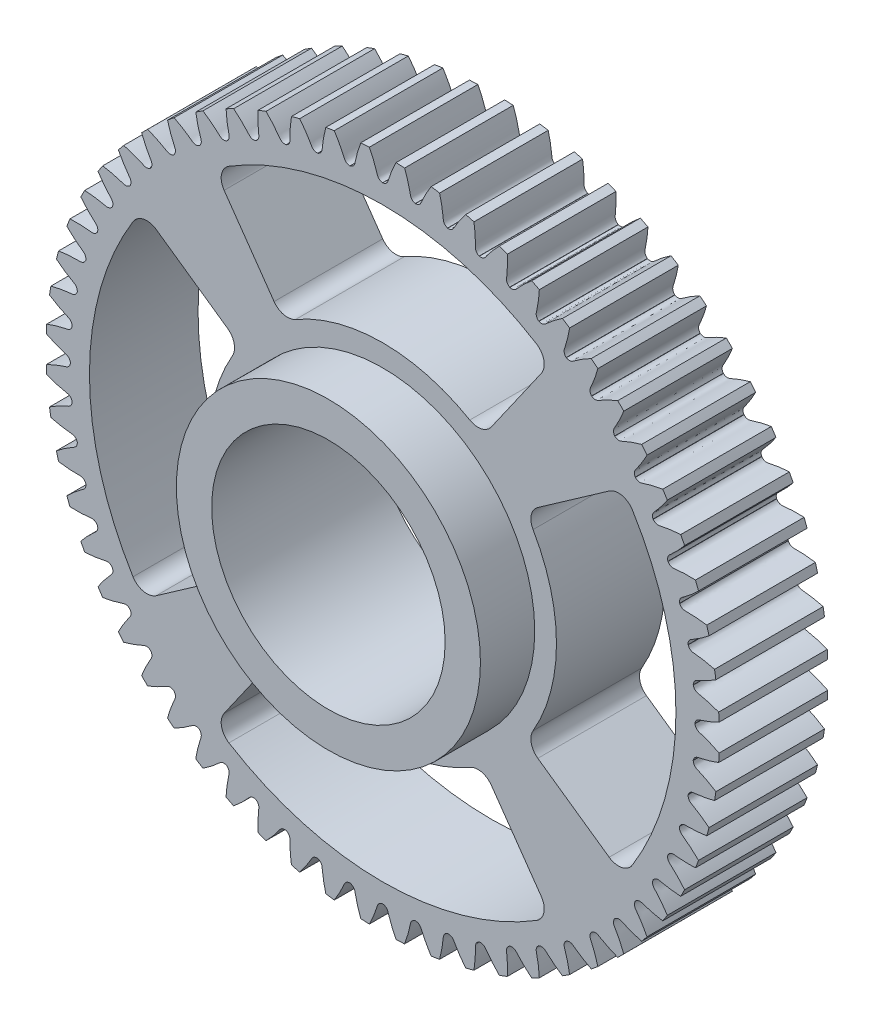
SolidWorks part; units mm, degrees
ref_plane "前视基准面" through (0, 0, 0) normal (0, 0, 1) x (1, 0, 0)
ref_plane "上视基准面" through (0, 0, 0) normal (0, 1, 0) x (1, 0, 0)
ref_plane "右视基准面" through (0, 0, 0) normal (1, 0, 0) x (0, 0, -1)
other "Configuration Table"
sketch "草图1" plane through (0, 0, 0) normal (0, 0, 1) x (1, 0, 0)
  circle A0 centre (0, 0) radius 31
extrude "凸台-拉伸1" add sketch "草图1" along normal blind 10
ref_axis "基准轴1" through (0, 0, -1.5) along (0, 0, 1)
sketch "草图2" plane through (0, 0, 0) normal (0, 0, 1) x (1, 0, 0)
  line L0 (0, 0) -> (0, 31) construction
  circle A0 centre (0, 0) radius 31 construction
  arc A1 (0.01, 28.75) -> (-0.01, 28.75) centre (0, 0) ccw
  arc A2 (4.2086, 35.0652) -> (-4.2086, 35.0652) centre (0, 0) ccw
  spline S0 degree 3 poles (0.01, 28.75) (0.4295, 28.8193) (0.4958, 29.1655) (0.6239, 29.5502) (0.684, 29.7232) (0.7519, 29.9052) (0.8274, 30.0965) (0.9111, 30.2965) (1.0033, 30.5052) (1.1044, 30.7222) (1.2149, 30.9473) (1.3349, 31.1801) (1.465, 31.4204) (1.6054, 31.6679) (1.7565, 31.9222) (1.9186, 32.183) (2.092, 32.45) (2.2771, 32.7228) (2.4741, 33.001) (2.6833, 33.2844) (2.905, 33.5724) (3.1395, 33.8647) (3.387, 34.1609) (3.7397, 34.5662) (4.0171, 34.8662) (4.2086, 35.0652) knots 0 0 0 0 0.112555 0.13496 0.158835 0.184181 0.210998 0.239286 0.269045 0.300275 0.332976 0.367147 0.40279 0.439904 0.478488 0.518544 0.56007 0.603067 0.647536 0.693475 0.740885 0.789766 0.840118 0.891941 1 1 1 1
  spline S1 degree 3 poles (-0.01, 28.75) (-0.4295, 28.8193) (-0.4958, 29.1655) (-0.6239, 29.5502) (-0.684, 29.7232) (-0.7519, 29.9052) (-0.8274, 30.0965) (-0.9111, 30.2965) (-1.0033, 30.5052) (-1.1044, 30.7222) (-1.2149, 30.9473) (-1.3349, 31.1801) (-1.465, 31.4204) (-1.6054, 31.6679) (-1.7565, 31.9222) (-1.9186, 32.183) (-2.092, 32.45) (-2.2771, 32.7228) (-2.4741, 33.001) (-2.6833, 33.2844) (-2.905, 33.5724) (-3.1395, 33.8647) (-3.387, 34.1609) (-3.7397, 34.5662) (-4.0171, 34.8662) (-4.2086, 35.0652) knots 0 0 0 0 0.112555 0.13496 0.158835 0.184181 0.210998 0.239286 0.269045 0.300275 0.332976 0.367147 0.40279 0.439904 0.478488 0.518544 0.56007 0.603067 0.647536 0.693475 0.740885 0.789766 0.840118 0.891941 1 1 1 1
extrude "切除-拉伸1" cut sketch "草图2" along normal through all
pattern_circular "阵列(圆周)1" count 60 over 360 about axis through (0, 0, -1.5) along (0, 0, 1) of "切除-拉伸1"
sketch "草图3" plane through (0, 0, 0) normal (0, 0, 1) x (1, 0, 0)
  circle A0 centre (0, 0) radius 30 construction
  dimension "Dn" = 60
sketch "草图4" plane through (0, 0, 10) normal (0, 0, 1) x (1, 0, 0)
  line L0 (0, 0) -> (0, -50000) construction
  line L1 (0, 0) -> (-50000, 0) construction
  line L2 (-10.0006, 14.2824) -> (-14.6009, 20.8522)
  line L3 (10.0006, 14.2824) -> (14.6009, 20.8522)
  line L4 (14.2824, -10.0006) -> (20.8522, -14.6009)
  line L5 (14.2824, 10.0006) -> (20.8522, 14.6009)
  line L6 (-10.0006, -14.2824) -> (-14.6009, -20.8522)
  line L7 (10.0006, -14.2824) -> (14.6009, -20.8522)
  line L8 (-14.2824, 10.0006) -> (-20.8522, 14.6009)
  line L9 (-14.2824, -10.0006) -> (-20.8522, -14.6009)
  circle A0 centre (0, 0) radius 14
  circle A1 centre (0, 0) radius 10.75
  arc A2 (-14.1587, 22.9898) -> (14.1587, 22.9898) centre (0, 0) cw
  arc A3 (-8.02, 13.8448) -> (8.02, 13.8448) centre (0, 0) cw
  arc A4 (-10.7419, 29.0794) -> (-11.4752, 28.7979) centre (0, 0) ccw construction
  arc A5 (10.0006, 14.2824) -> (8.02, 13.8448) centre (8.7719, 15.1428) cw
  arc A6 (14.6009, 20.8522) -> (14.1587, 22.9898) centre (13.3721, 21.7126) ccw
  arc A7 (-14.6009, 20.8522) -> (-14.1587, 22.9898) centre (-13.3721, 21.7126) cw
  arc A8 (-10.0006, 14.2824) -> (-8.02, 13.8448) centre (-8.7719, 15.1428) ccw
  arc A9 (13.8448, 8.02) -> (13.8448, -8.02) centre (0, 0) cw
  arc A10 (14.2824, 10.0006) -> (13.8448, 8.02) centre (15.1428, 8.7719) ccw
  arc A11 (14.2824, -10.0006) -> (13.8448, -8.02) centre (15.1428, -8.7719) cw
  arc A12 (20.8522, -14.6009) -> (22.9898, -14.1587) centre (21.7126, -13.3721) ccw
  arc A13 (22.9898, 14.1587) -> (22.9898, -14.1587) centre (0, 0) cw
  arc A14 (20.8522, 14.6009) -> (22.9898, 14.1587) centre (21.7126, 13.3721) cw
  arc A15 (8.02, -13.8448) -> (-8.02, -13.8448) centre (0, 0) cw
  arc A16 (10.0006, -14.2824) -> (8.02, -13.8448) centre (8.7719, -15.1428) ccw
  arc A17 (-10.0006, -14.2824) -> (-8.02, -13.8448) centre (-8.7719, -15.1428) cw
  arc A18 (-14.6009, -20.8522) -> (-14.1587, -22.9898) centre (-13.3721, -21.7126) ccw
  arc A19 (14.1587, -22.9898) -> (-14.1587, -22.9898) centre (0, 0) cw
  arc A20 (14.6009, -20.8522) -> (14.1587, -22.9898) centre (13.3721, -21.7126) cw
  arc A21 (-13.8448, -8.02) -> (-13.8448, 8.02) centre (0, 0) cw
  arc A22 (-14.2824, -10.0006) -> (-13.8448, -8.02) centre (-15.1428, -8.7719) ccw
  arc A23 (-14.2824, 10.0006) -> (-13.8448, 8.02) centre (-15.1428, 8.7719) cw
  arc A24 (-20.8522, 14.6009) -> (-22.9898, 14.1587) centre (-21.7126, 13.3721) ccw
  arc A25 (-22.9898, -14.1587) -> (-22.9898, 14.1587) centre (0, 0) cw
  arc A26 (-20.8522, -14.6009) -> (-22.9898, -14.1587) centre (-21.7126, -13.3721) cw
  point P17 (9.1772, 13.1064)
  point P20 (15.4866, 22.1171)
  point P23 (-15.4866, 22.1171)
  point P26 (-9.1772, 13.1064)
  point P66 (0, 0)
  dimension "D1" = 21.5
  dimension "D2" = 28
  dimension "D3" = 4
  dimension "D4" = 2
  dimension "D6" = 1.5
  dimension "D5" = 35
  dimension "D7" = 4
extrude "切除-拉伸3" cut sketch "草图4" against normal through all contours A26 L9 A22 A21 A23 L8 A24 A25 | L2 A8 A3 A5 L3 A6 A2 A7 | A14 L5 A10 A9 A11 L4 A12 A13 | A20 L7 A16 A15 A17 L6 A18 A19 | A1 | L8 A24 A25 A26 L9 A22 A21 A23 region at (0, 20.6436, 10) region at (20.6436, 0, 10) region at (0, -20.6436, 10) region at (-20.6436, 0, 10) region at (0, 0, 10)
sketch "草图5" plane through (0, 0, 10) normal (0, 0, 1) x (1, 0, 0)
  circle A0 centre (0, 0) radius 14
  arc A1 (13.8448, -8.02) -> (13.8448, 8.02) centre (0, 0) ccw construction
  circle A2 centre (0, 0) radius 10.75 construction
  circle A3 centre (0, 0) radius 10.75
  dimension "D1" = 2
extrude "凸台-拉伸3" add sketch "草图5" along normal blind 5
